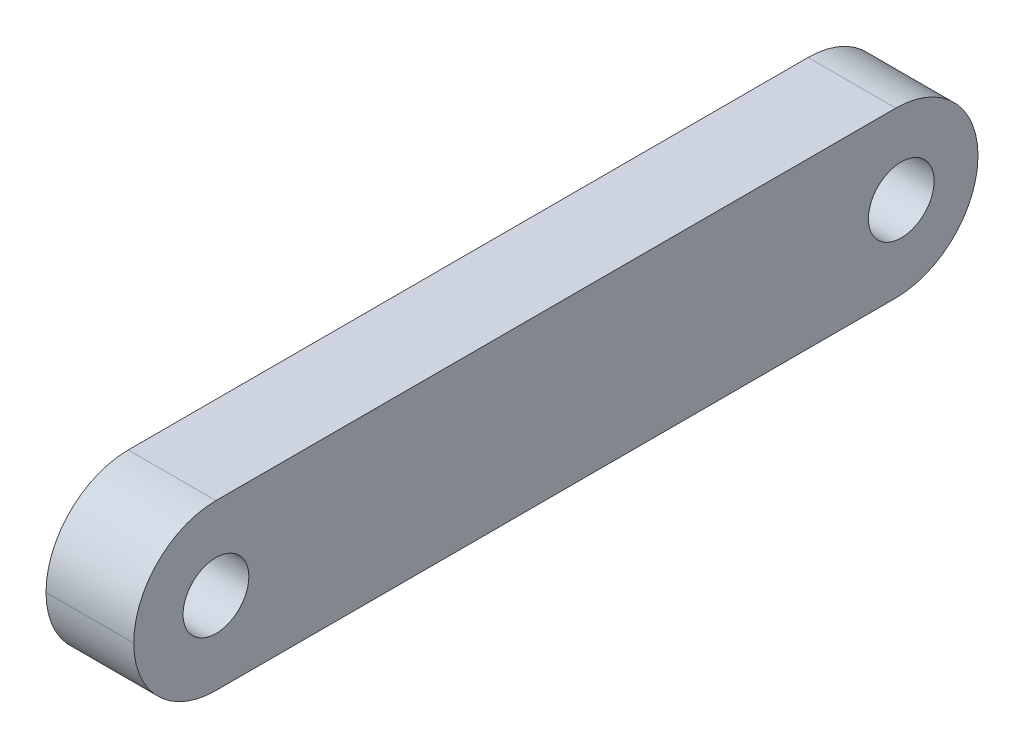
SolidWorks part; units mm, degrees
ref_plane "前视基准面" through (0, 0, 0) normal (0, 0, 1) x (1, 0, 0)
ref_plane "上视基准面" through (0, 0, 0) normal (0, 1, 0) x (1, 0, 0)
ref_plane "右视基准面" through (0, 0, 0) normal (1, 0, 0) x (0, 0, -1)
other "Configuration Table"
sketch "草图1" plane through (0, 0, 0) normal (1, 0, 0) x (0, 0, -1)
  line L5 (0, 0) -> (15.4, 0)
  line L6 (0, 0) -> (0, -3)
  line L7 (0, -3) -> (15.4, -3)
  line L8 (15.4, 0) -> (15.4, -3)
  circle A3 centre (1.5, -1.5) radius 0.6
  circle A4 centre (14, -1.5) radius 0.6
  point P8 (0, 0)
  point P9 (0, -1.5)
  dimension "D1" = 1.5
  dimension "D2" = 1.2
  dimension "D3" = 1.4
  dimension "D4" = 12.5
  dimension "D5" = 3
extrude "凸台-拉伸1" add sketch "草图1" along normal blind 1.6 contours L7 L8 L5 L6 | A3 | A4
fillet "圆角1" radius 1.5 4 edges at (0.8, -3, 0) (0.8, 0, 0) (0.8, -3, -15.4) (0.8, 0, -15.4)
